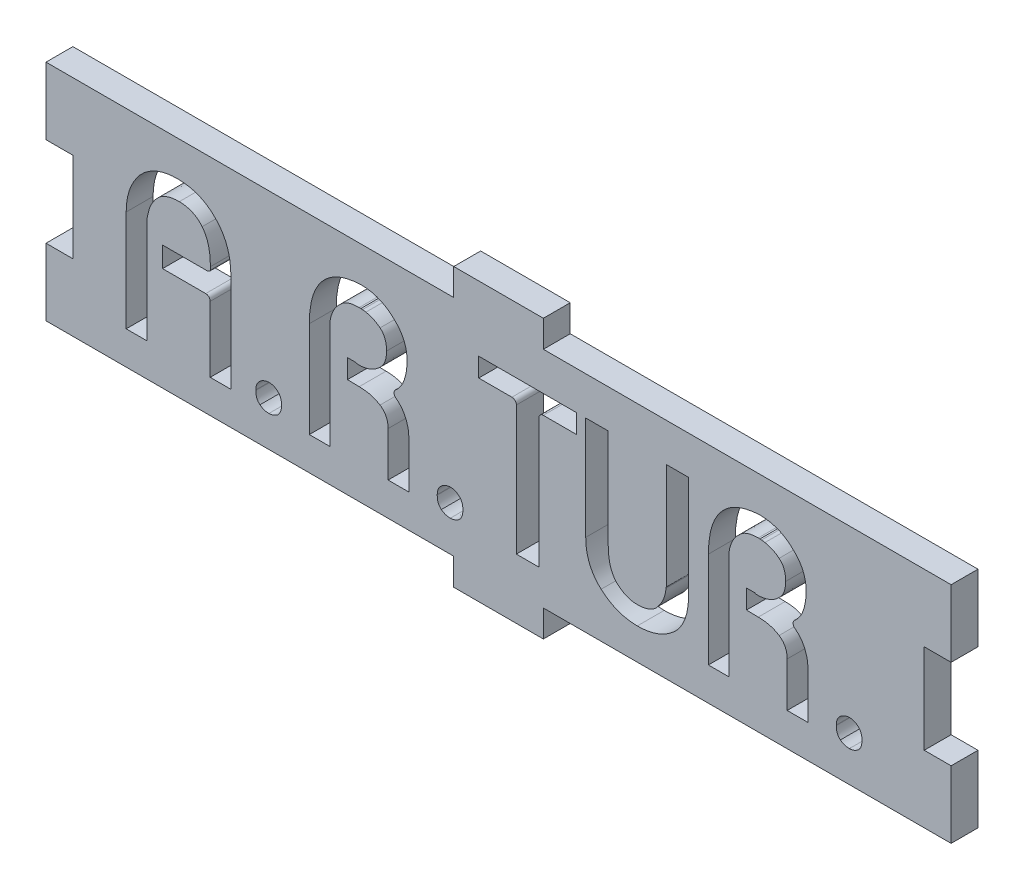
SolidWorks part; units mm, degrees
ref_plane "Plan de face" through (0, 0, 0) normal (0, 0, 1) x (1, 0, 0)
ref_plane "Plan de dessus" through (0, 0, 0) normal (0, 1, 0) x (1, 0, 0)
ref_plane "Plan de droite" through (0, 0, 0) normal (1, 0, 0) x (0, 0, -1)
sketch "Esquisse1" plane through (0, 0, 0) normal (0, 0, 1) x (1, 0, 0)
  line L0 (0, 0) -> (0, 4.9998) construction
  line L1 (0, 0) -> (10.4157, 0) construction
  line L2 (-101, 25) -> (101, 25)
  line L3 (101, 25) -> (101, -25)
  line L4 (-101, 25) -> (-101, -25)
  line L5 (-101, -25) -> (101, -25)
  point P9 (0, 25)
  point P10 (-101, 0)
  point P11 (101, 0)
  dimension "D1" = 101
  dimension "D2" = 25
extrude "Boss.-Extru.1" add sketch "Esquisse1" along normal blind 6
sketch "Esquisse3" plane through (0, 0, 6) normal (0, 0, 1) x (1, 0, 0)
  line L0 (-101, 25) -> (-101, -25) construction
  line L2 (-101, -25) -> (101, -25) construction
  line L3 (0, 0) -> (0, 50.5726) construction
  line L4 (0, 0) -> (128.9274, 0) construction
  line L5 (-85, -17.6) -> (130.6748, -17.6) construction
  line L6 (-85, -17.6) -> (-85, 56.622) construction
  line L7 (85, -17.6) -> (85, 56.622) construction
  line L8 (-85, 17.6) -> (130.6748, 17.6) construction
  line L9 (101, -25) -> (101, 25) construction
  line L10 (101, 25) -> (-101, 25) construction
  text T0 "A.R.TUR." font "Bauhaus" height in points 135
  dimension "D1" = 16
  dimension "D2" = 7.4
  dimension "D3" = 16
  dimension "D4" = 7.4
extrude "Enlèv. mat.-Extru.3" cut sketch "Esquisse3" against normal up to next
sketch "Esquisse4" plane through (0, 0, 6) normal (0, 0, 1) x (1, 0, 0)
  line L0 (0, 0) -> (0, 61.9969) construction
  line L1 (-101, 10) -> (-95, 10)
  line L2 (-101, 10) -> (-101, -10)
  line L3 (-101, -10) -> (-95, -10)
  line L4 (-95, 10) -> (-95, -10)
  line L5 (0, 0) -> (125.929, 0) construction
  line L6 (-101, 25) -> (-101, -25) construction
  line L7 (-101, 0) -> (-95, 0) construction
  line L8 (101, 10) -> (95, 10)
  line L9 (95, 10) -> (95, -10)
  line L10 (101, 10) -> (101, -10)
  line L11 (101, -10) -> (95, -10)
  dimension "D1" = 20
  dimension "D2" = 6
extrude "Enlèv. mat.-Extru.4" cut sketch "Esquisse4" against normal up to next
sketch "Esquisse5" plane through (0, 0, 6) normal (0, 0, 1) x (1, 0, 0)
  line L0 (0, 0) -> (0, 53.4988) construction
  line L1 (0, 0) -> (102.3498, 0) construction
  line L2 (-10, 25) -> (-10, 31)
  line L3 (101, 25) -> (-101, 25) construction
  line L4 (-10, 31) -> (10, 31)
  line L5 (10, 25) -> (10, 31)
  line L6 (10, 25) -> (-10, 25)
  line L7 (10, -25) -> (10, -31)
  line L8 (-10, -31) -> (10, -31)
  line L9 (-10, -25) -> (-10, -31)
  line L10 (10, -25) -> (-10, -25)
  point P11 (0, 31)
  dimension "D1" = 10
  dimension "D2" = 6
extrude "Boss.-Extru.2" add sketch "Esquisse5" against normal blind 6
sketch "Esquisse6" plane through (-76.9878, 0, 0) normal (1, 0, 0) x (0, 0, -1)
  line L4 (0, -1.9059) -> (0, 2.6554)
  line L5 (0, 2.6554) -> (-6, 2.6554)
  line L6 (-6, 2.6554) -> (-6, -1.9059)
  line L7 (-6, -1.9059) -> (0, -1.9059)
  line L8 (0, -1.9059) -> (0, 2.6554)
  line L9 (0, 2.6554) -> (-6, 2.6554)
  line L10 (-6, 2.6554) -> (-6, -1.9059)
  line L11 (-6, -1.9059) -> (0, -1.9059)
  dimension "D1" = 0
extrude "Boss.-Extru.3" add sketch "Esquisse6" along normal blind 2
sketch "Esquisse7" plane through (-35.7249, 0, 0) normal (1, 0, 0) x (0, 0, -1)
  line L4 (0, -2.6861) -> (0, 1.5379)
  line L5 (0, 1.5379) -> (-6, 1.5379)
  line L6 (-6, 1.5379) -> (-6, -2.6861)
  line L7 (-6, -2.6861) -> (0, -2.6861)
  line L8 (0, -2.6861) -> (0, 1.5379)
  line L9 (0, 1.5379) -> (-6, 1.5379)
  line L10 (-6, 1.5379) -> (-6, -2.6861)
  line L11 (-6, -2.6861) -> (0, -2.6861)
  dimension "D1" = 0
extrude "Boss.-Extru.4" add sketch "Esquisse7" along normal blind 2
sketch "Esquisse8" plane through (53.3371, 0, 0) normal (1, 0, 0) x (0, 0, -1)
  line L4 (0, -2.6861) -> (0, 1.5379)
  line L5 (0, 1.5379) -> (-6, 1.5379)
  line L6 (-6, 1.5379) -> (-6, -2.6861)
  line L7 (-6, -2.6861) -> (0, -2.6861)
  line L8 (0, -2.6861) -> (0, 1.5379)
  line L9 (0, 1.5379) -> (-6, 1.5379)
  line L10 (-6, 1.5379) -> (-6, -2.6861)
  line L11 (-6, -2.6861) -> (0, -2.6861)
  dimension "D1" = 0
extrude "Boss.-Extru.5" add sketch "Esquisse8" along normal blind 2
sketch "Esquisse9" plane through (0, -2.6861, 0) normal (0, -1, 0) x (1, 0, 0)
  line L4 (-35.7249, 6) -> (-35.7249, 0)
  line L5 (-35.7249, 0) -> (-33.7249, 0)
  line L6 (-33.7249, 0) -> (-33.7249, 6)
  line L7 (-33.7249, 6) -> (-35.7249, 6)
  line L8 (-35.7249, 6) -> (-35.7249, 0)
  line L9 (-35.7249, 0) -> (-33.7249, 0)
  line L10 (-33.7249, 0) -> (-33.7249, 6)
  line L11 (-33.7249, 6) -> (-35.7249, 6)
  dimension "D1" = 0
extrude "Boss.-Extru.6" add sketch "Esquisse9" along normal up to next
sketch "Esquisse10" plane through (0, -2.6861, 0) normal (0, -1, 0) x (1, 0, 0)
  line L4 (53.3371, 6) -> (53.3371, 0)
  line L5 (53.3371, 0) -> (55.3371, 0)
  line L6 (55.3371, 0) -> (55.3371, 6)
  line L7 (55.3371, 6) -> (53.3371, 6)
  line L8 (53.3371, 6) -> (53.3371, 0)
  line L9 (53.3371, 0) -> (55.3371, 0)
  line L10 (55.3371, 0) -> (55.3371, 6)
  line L11 (55.3371, 6) -> (53.3371, 6)
  dimension "D1" = 0
extrude "Boss.-Extru.7" add sketch "Esquisse10" along normal up to next
fillet "Congé1" radius 1 1 edges at (-24.2619, -0.1137, 3)
fillet "Congé2" radius 1 2 edges at (-64.351, -1.9059, 3) (-64.351, 2.6554, 3)
fillet "Congé3" radius 1 1 edges at (-64.3018, 3.049, 3)
fillet "Congé5" radius 1 2 edges at (8.9818, 12.2279, 3) (3.9777, 12.2279, 3)
fillet "Congé6" radius 1 1 edges at (64.8001, -0.1137, 3)
